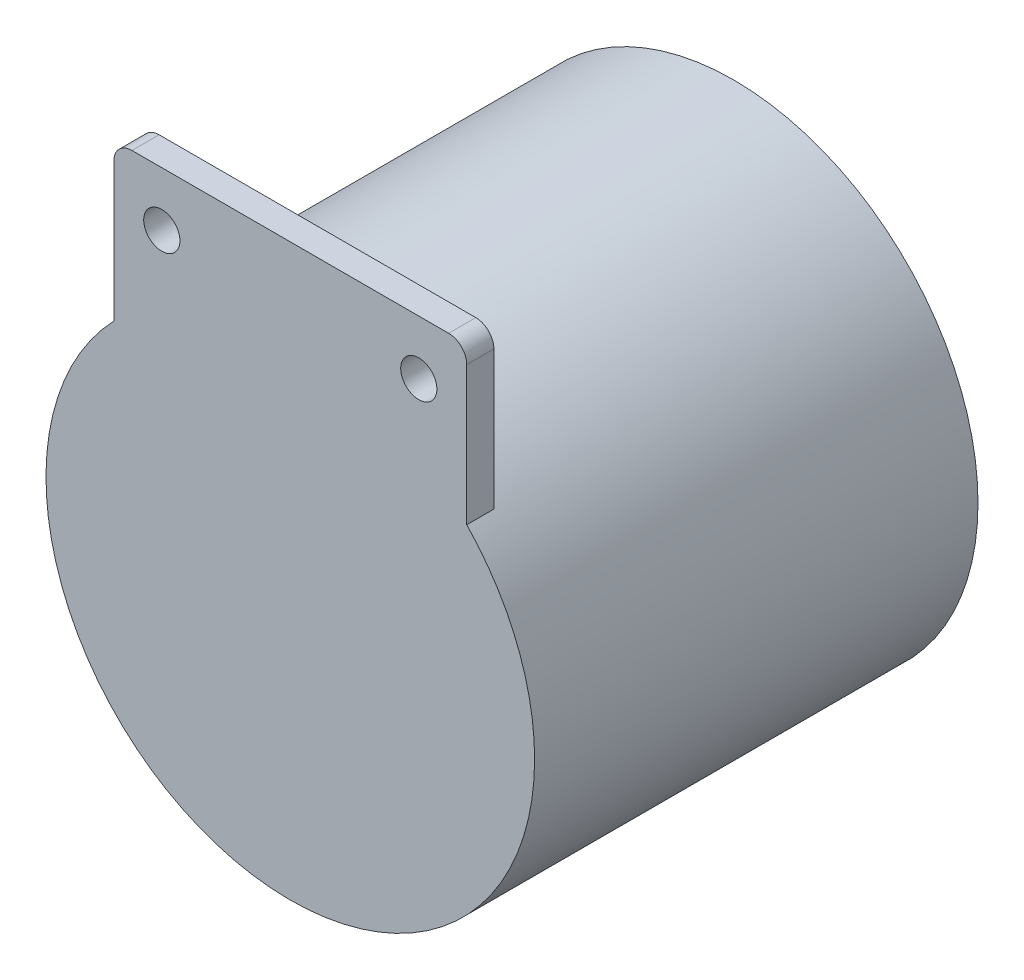
SolidWorks part; units mm, degrees
ref_plane "Plan de face" through (0, 0, 0) normal (0, 0, 1) x (1, 0, 0)
ref_plane "Plan de dessus" through (0, 0, 0) normal (0, 1, 0) x (1, 0, 0)
ref_plane "Plan de droite" through (0, 0, 0) normal (1, 0, 0) x (0, 0, -1)
sketch "Esquisse1" plane through (0, 0, 0) normal (0, 0, 1) x (1, 0, 0)
  circle A0 centre (0, 0) radius 27
  dimension "D1" = 54
extrude "Boss.-Extru.1" add sketch "Esquisse1" against normal blind 49
sketch "Esquisse2" plane through (0, 0, 0) normal (0, 0, 1) x (1, 0, 0)
  line L0 (-18.2781, -27) -> (31.0834, -27) construction
  line L2 (-19.5, 18.6748) -> (-19.5, 36)
  line L3 (-19.5, 36) -> (19.5, 36)
  line L4 (19.5, 18.6748) -> (19.5, 36)
  line L5 (0, 27) -> (0, -27) construction
  arc A0 (19.5, 18.6748) -> (-19.5, 18.6748) centre (0, 0) ccw
  circle A1 centre (0, 0) radius 27 construction
  circle A2 centre (-14.2, 30) radius 2
  circle A3 centre (14.2, 30) radius 2
  dimension "D4" = 6
  dimension "D6" = 4
  dimension "D1" = 63
  dimension "D2" = 39
  dimension "D3" = 19.5
  dimension "D5" = 5.3
extrude "Boss.-Extru.2" add sketch "Esquisse2" against normal blind 3
fillet "Congé1" radius 2 2 edges at (-19.5, 36, -1.5) (19.5, 36, -1.5)
